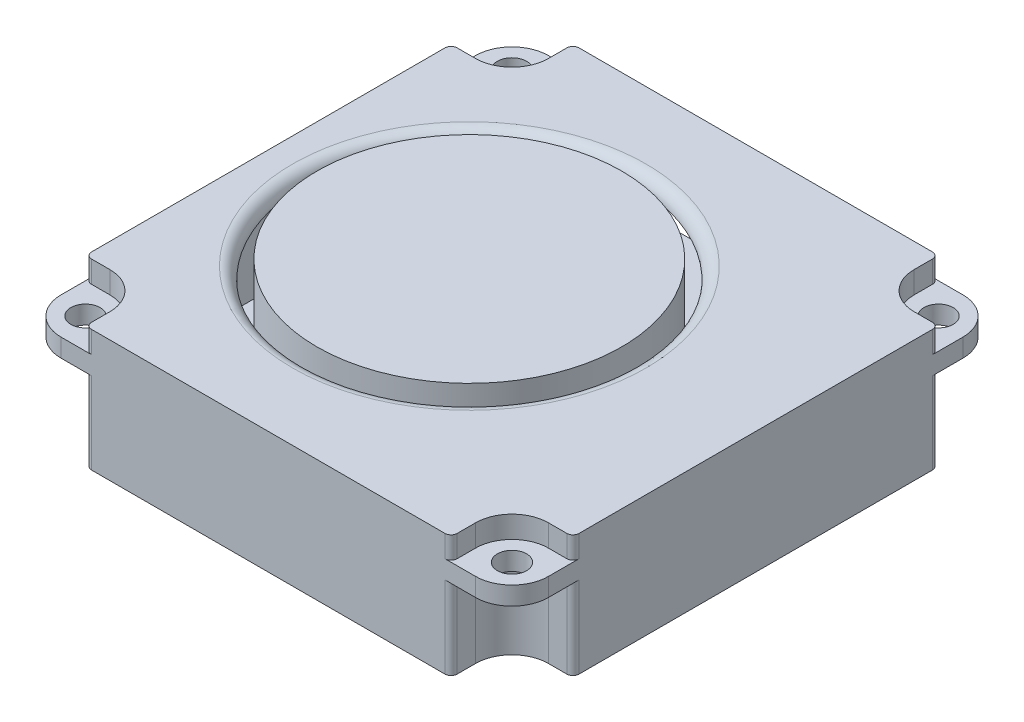
SolidWorks part; units mm, degrees
material "ABS"
ref_plane "正面" through (0, 0, 0) normal (0, 0, 1) x (1, 0, 0)
ref_plane "平面" through (0, 0, 0) normal (0, 1, 0) x (1, 0, 0)
ref_plane "右側面" through (0, 0, 0) normal (1, 0, 0) x (0, 0, -1)
sketch "ｽｹｯﾁ1" plane through (0, 0, 0) normal (0, 1, 0) x (1, 0, 0)
  line L1 (20, -20) -> (-20, -20)
  line L2 (20, -20) -> (20, 20)
  line L3 (20, 20) -> (-20, 20)
  line L4 (-20, -20) -> (-20, 20)
  line L5 (20, -20) -> (-20, 20) construction
  line L6 (20, 20) -> (-20, -20) construction
  point P0 (0, 0)
  dimension "D1" = 40
extrude "ﾎﾞｽ - 押し出し1" add sketch "ｽｹｯﾁ1" along normal mid plane 10
sketch "ｽｹｯﾁ2" plane through (0, 5, 0) normal (0, 1, 0) x (1, 0, 0)
  line L1 (20, 20) -> (15, 20)
  line L2 (20, 20) -> (20, 15)
  line L3 (20, 15) -> (15, 15)
  line L4 (15, 20) -> (15, 15)
  line L5 (0, 20) -> (0, 0) construction
  line L6 (20, 20) -> (-20, 20) construction
  line L7 (0, 0) -> (20, 0) construction
  line L8 (20, -20) -> (20, 20) construction
  line L9 (-15, 20) -> (-15, 15)
  line L10 (-20, 15) -> (-15, 15)
  line L11 (-20, 20) -> (-20, 15)
  line L12 (-20, 20) -> (-15, 20)
  line L13 (-20, -20) -> (-15, -20)
  line L14 (-20, -20) -> (-20, -15)
  line L15 (-20, -15) -> (-15, -15)
  line L16 (-15, -20) -> (-15, -15)
  line L17 (15, -20) -> (15, -15)
  line L18 (20, -15) -> (15, -15)
  line L19 (20, -20) -> (20, -15)
  line L20 (20, -20) -> (15, -20)
  dimension "D1" = 5
extrude "ｶｯﾄ - 押し出し1" cut sketch "ｽｹｯﾁ2" against normal blind 1.8
sketch "ｽｹｯﾁ4" plane through (0, -5, 0) normal (0, -1, 0) x (1, 0, 0)
  line L4 (15, -20) -> (20, -20)
  line L5 (15, -15) -> (15, -20)
  line L6 (20, -15) -> (15, -15)
  line L7 (20, -20) -> (20, -15)
  line L8 (15, -20) -> (20, -20)
  line L9 (15, -15) -> (15, -20)
  line L10 (20, -15) -> (15, -15)
  line L11 (20, -20) -> (20, -15)
  line L12 (15, 20) -> (15, 15)
  line L13 (15, 15) -> (20, 15)
  line L14 (20, 15) -> (20, 20)
  line L15 (20, 20) -> (15, 20)
  line L16 (15, 20) -> (15, 15)
  line L17 (15, 15) -> (20, 15)
  line L18 (20, 15) -> (20, 20)
  line L19 (20, 20) -> (15, 20)
  line L20 (-15, 20) -> (-20, 20)
  line L21 (-15, 15) -> (-15, 20)
  line L22 (-20, 15) -> (-15, 15)
  line L23 (-20, 20) -> (-20, 15)
  line L24 (-15, 20) -> (-20, 20)
  line L25 (-15, 15) -> (-15, 20)
  line L26 (-20, 15) -> (-15, 15)
  line L27 (-20, 20) -> (-20, 15)
  line L28 (-20, -15) -> (-20, -20)
  line L29 (-15, -15) -> (-20, -15)
  line L30 (-15, -20) -> (-15, -15)
  line L31 (-20, -20) -> (-15, -20)
  line L32 (-20, -15) -> (-20, -20)
  line L33 (-15, -15) -> (-20, -15)
  line L34 (-15, -20) -> (-15, -15)
  line L35 (-20, -20) -> (-15, -20)
  dimension "D1" = 0
  dimension "D2" = 0
  dimension "D3" = 0
  dimension "D4" = 0
extrude "ｶｯﾄ - 押し出し2" cut sketch "ｽｹｯﾁ4" against normal blind 6.7
fillet "ﾌｨﾚｯﾄ1" radius 3 12 edges at (-15, 4.1, -15) (15, 4.1, -15) (15, 4.1, 15) (-15, 4.1, 15) (-15, -1.65, 15) (-15, -1.65, -15) (15, -1.65, -15) (15, -1.65, 15) (20, 2.45, 20) (-20, 2.45, 20) (-20, 2.45, -20) (20, 2.45, -20)
hole_wizard "M2 すきま穴1" positions "ｽｹｯﾁ5" profile "ｽｹｯﾁ6" hole size "M2" standard "JIS" end condition through all
sketch "ｽｹｯﾁ5" plane through (0, 3.2, 0) normal (0, 1, 0) x (1, 0, 0)
  line L0 (-20, 0) -> (0, 0) construction
  line L1 (-20, 15) -> (-20, -15) construction
  line L3 (0, 0) -> (0, 20) construction
  line L4 (15, 20) -> (-15, 20) construction
  point P0 (-17.5, -17.5)
  point P9 (-17.5, 17.5)
  point P16 (17.5, 17.5)
  point P17 (17.5, -17.5)
  dimension "D1" = 35
  dimension "D2" = 35
sketch "ｽｹｯﾁ6" plane through (-17.5, 3.2, 17.5) normal (1, 0, 0) x (0, 0, 1)
  line L0 (0, 0) -> (0, 8.2)
  line L1 (0, 8.2) -> (1.2, 8.2)
  line L2 (1.2, 8.2) -> (1.2, 0)
  line L5 (1.2, 0) -> (0, 0)
  line L11 (0, -6.35) -> (0, 107.95) construction
  dimension "通し穴の直径" = 2.4
  dimension "通し穴の深さ" = 8.2
fillet "ﾌｨﾚｯﾄ2" radius 0.5 16 edges at (-15, 4.1, -20) (15, 4.1, -20) (20, 4.1, -15) (20, 4.1, 15) (-20, 4.1, -15) (15, 4.1, 20) (20, -1.65, -15) (15, -1.65, 20) (20, -1.65, 15) (15, -1.65, -20) (-15, -1.65, -20) (-20, -1.65, -15) (-15, -1.65, 20) (-20, -1.65, 15) (-20, 4.1, 15) (-15, 4.1, 20)
sketch "ｽｹｯﾁ8" plane through (0, 0, 0) normal (0, 1, 0) x (1, 0, 0)
  line L12 (-14, 19) -> (-14, 20)
  line L13 (14.5, 20) -> (-14.5, 20) construction
  line L14 (-14, 20) -> (14, 20)
  line L15 (14, 20) -> (14, 19)
  line L24 (19, 14) -> (18, 14)
  line L25 (19, -14) -> (19, 14)
  line L26 (18, -14) -> (19, -14)
  line L27 (14, -19) -> (14, -18)
  line L28 (-14, -19) -> (14, -19)
  line L29 (-14, -18) -> (-14, -19)
  line L30 (-19, -14) -> (-18, -14)
  line L31 (-19, 14) -> (-19, -14)
  line L32 (-18, 14) -> (-19, 14)
  line L33 (-14, 19) -> (-14, 18)
  line L34 (14, 19) -> (-14, 19)
  line L35 (14, 18) -> (14, 19)
  line L36 (19, 14) -> (18, 14)
  line L37 (19, -14) -> (19, 14)
  line L38 (18, -14) -> (19, -14)
  line L39 (14, -19) -> (14, -18)
  line L40 (-14, -19) -> (14, -19)
  line L41 (-14, -18) -> (-14, -19)
  line L42 (-19, -14) -> (-18, -14)
  line L43 (-19, 14) -> (-19, -14)
  line L44 (-18, 14) -> (-19, 14)
  line L45 (-14, 19) -> (-14, 18)
  line L47 (14, 18) -> (14, 19)
  arc A24 (18, -14) -> (14, -18) centre (18, -18) ccw
  arc A25 (-14, -18) -> (-18, -14) centre (-18, -18) ccw
  arc A26 (-18, 14) -> (-14, 18) centre (-18, 18) ccw
  arc A27 (14, 18) -> (18, 14) centre (18, 18) ccw
  arc A28 (18, -14) -> (14, -18) centre (18, -18) ccw
  arc A29 (-14, -18) -> (-18, -14) centre (-18, -18) ccw
  arc A30 (-18, 14) -> (-14, 18) centre (-18, 18) ccw
  arc A31 (14, 18) -> (18, 14) centre (18, 18) ccw
  dimension "D1" = 1
extrude "ｶｯﾄ - 押し出し3" cut sketch "ｽｹｯﾁ8" against normal mid plane 8
sketch "ｽｹｯﾁ7" plane through (0, 5, 0) normal (0, -1, 0) x (1, 0, 0)
  line L0 (20, 14.5) -> (20, -14.5) construction
  line L1 (-3.5, 0) -> (0, 0) construction
  circle A0 centre (-3.5, 0) radius 13.5
  dimension "D1" = 27
  dimension "D2" = 23.5
extrude "ｶｯﾄ - 押し出し4" cut sketch "ｽｹｯﾁ7" along normal up to surface (9 mm away) up to face at (0, -4, -0.125)
fillet "ﾌｨﾚｯﾄ3" radius 1 1 edges at (-3.5, 5, -13.5)
sketch "ｽｹｯﾁ9" plane through (0, -4, 0) normal (0, 1, 0) x (1, 0, 0)
  circle A0 centre (-3.5, 0) radius 12.5
  dimension "D1" = 25
extrude "ﾎﾞｽ - 押し出し2" add sketch "ｽｹｯﾁ9" along normal offset from surface (9.5 mm away) 0.5 up to face at (-3.5, 5, 14.5) offset beyond the face yes
